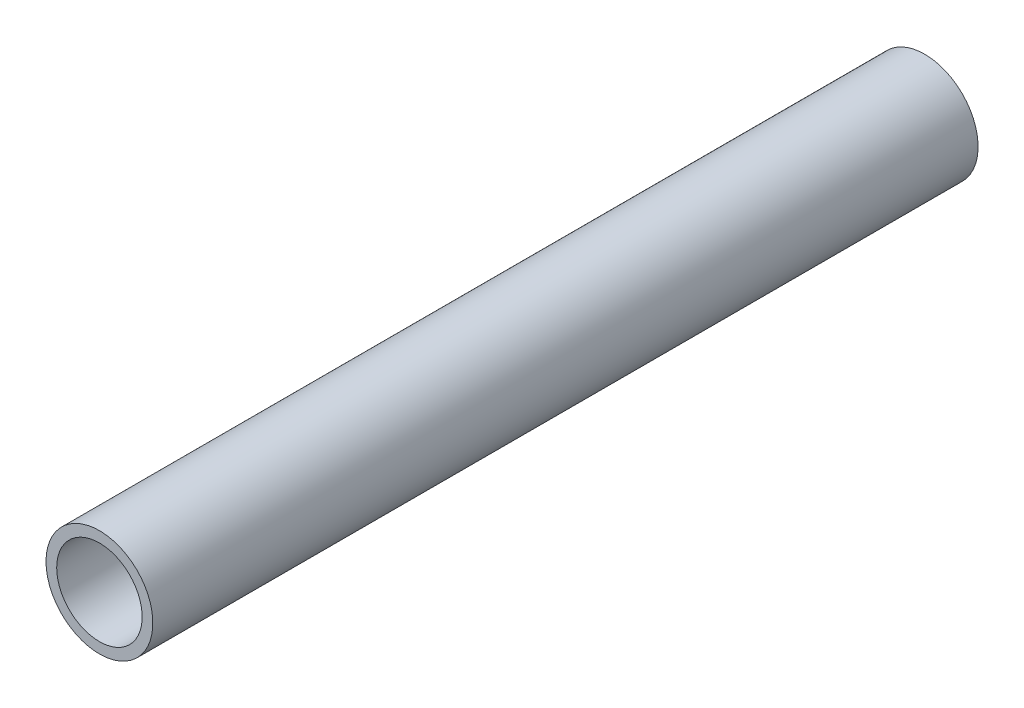
SolidWorks part; units mm, degrees
ref_plane "Front Plane" through (0, 0, 0) normal (0, 0, 1) x (1, 0, 0)
ref_plane "Top Plane" through (0, 0, 0) normal (0, 1, 0) x (1, 0, 0)
ref_plane "Right Plane" through (0, 0, 0) normal (1, 0, 0) x (0, 0, -1)
sketch "Sketch1" plane through (0, 0, 0) normal (0, 0, 1) x (1, 0, 0)
  circle A0 centre (0, 0) radius 1.25
  circle A1 centre (0, 0) radius 1
extrude "Boss-Extrude1" add sketch "Sketch1" along normal blind 19.31
